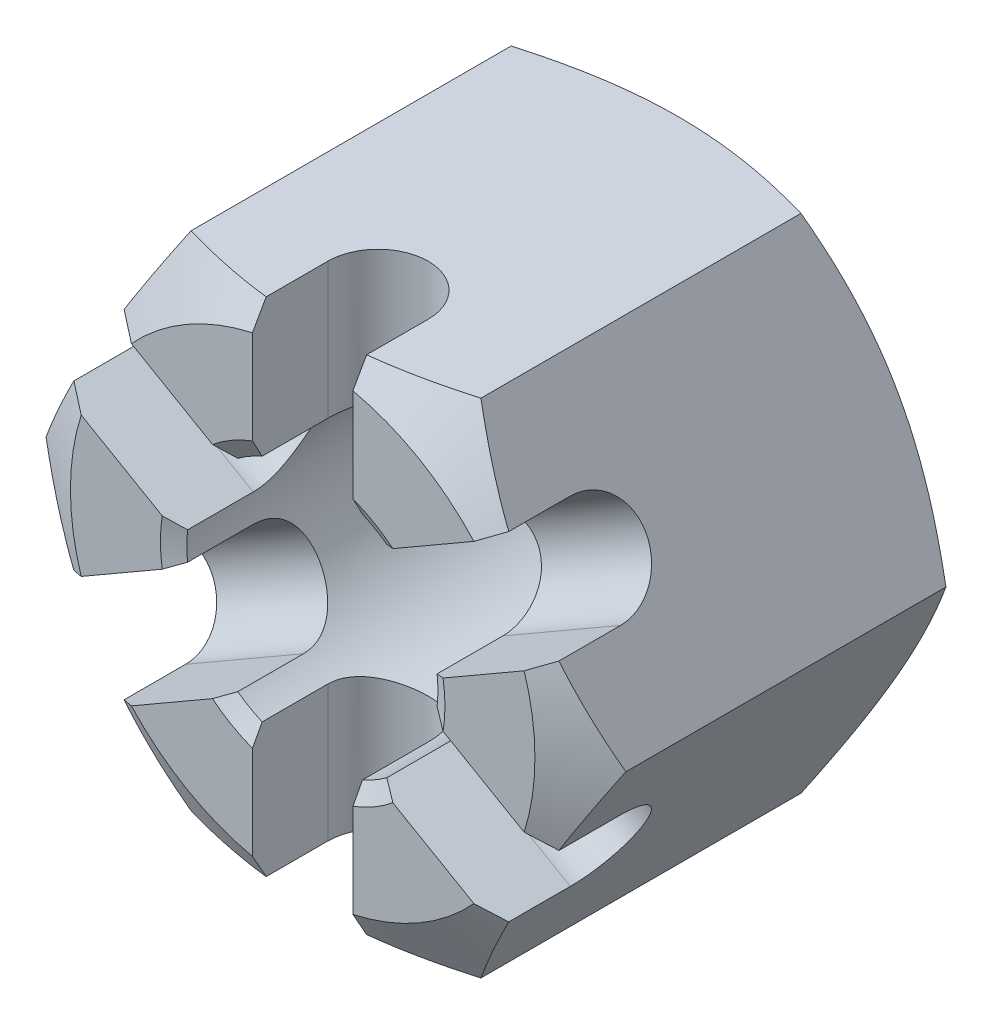
SolidWorks part; units mm, degrees
ref_plane "Front" through (0, 0, 0) normal (0, 0, 1) x (1, 0, 0)
ref_plane "Top" through (0, 0, 0) normal (0, 1, 0) x (1, 0, 0)
ref_plane "Right" through (0, 0, 0) normal (1, 0, 0) x (0, 0, -1)
sketch "Sketch1" plane through (0, 0, 0) normal (0, 0, 1) x (1, 0, 0)
  line L1 (2.8868, -5) -> (5.7735, 0)
  line L2 (5.7735, 0) -> (2.8868, 5)
  line L3 (2.8868, 5) -> (-2.8868, 5)
  line L4 (-2.8868, 5) -> (-5.7735, 0)
  line L5 (-5.7735, 0) -> (-2.8868, -5)
  line L6 (-2.8868, -5) -> (2.8868, -5)
  circle A0 centre (0, 0) radius 5 construction
  circle A1 centre (0, 0) radius 2.5
extrude "BaseNut" add sketch "Sketch1" against normal blind 7.7
cosmetic thread "ThreadCosmetic1" [suppressed] parameters "D"=6
sketch "Sketch2" plane through (0, 0, 0) normal (0, 1, 0) x (1, 0, 0)
  line L0 (-5.7735, 7.7) -> (-4.625, 7.7)
  line L2 (-4.625, 7.7) -> (-5.7735, 7.0369)
  line L3 (-5.7735, 7.0369) -> (-5.7735, 7.7)
  line L4 (0, 3.3759) -> (0, -9.8171) construction
  line L6 (-9.7712, 3.85) -> (9.8853, 3.85) construction
  line L7 (-5.7735, 0.6631) -> (-5.7735, 0)
  line L8 (-4.625, 0) -> (-5.7735, 0.6631)
  line L9 (-5.7735, 0) -> (-4.625, 0)
  dimension "D1" = 30
  dimension "D2" = 3.85
revolve "Double-Chamfer" cut sketch "Sketch2" angle 360 about L4
chamfer "EndChamfer" distance 0.3333 angle 30 2 edges at (2.5, 0, -7.7) (2.5, 0, 0) first distance on face at (2.5, 0, -7.7) first distance on face at (-4.625, 0, 0)
sketch "Sketch3" plane through (0, 0, 0) normal (0, 1, 0) x (1, 0, 0)
  line L0 (0, 4.2201) -> (0, -10.5237) construction
  line L1 (-2.8333, 0) -> (2.8333, 0) construction
  line L2 (-1, 0) -> (-1, 1.5)
  line L3 (1, 0) -> (1, 1.5)
  line L4 (2.6925, 7.7) -> (-2.6925, 7.7) construction
  arc A0 (-1, 1.5) -> (1, 1.5) centre (0, 1.5) cw
  point P2 (0, 2.5)
  point P3 (0, 7.7)
  dimension "D1" = 2.5
  dimension "W" = 5.2
extrude "Slot" cut sketch "Sketch3" against normal through all and the other way through all
ref_axis "Axis1" through (0, 0, 9.8171) along (0, 0, -1)
pattern_circular "SlotPattern" count 3 over 360 about axis through (0, 0, -3.3759) along (0, 0, 1) of "Slot"
sketch "Sketch4" plane through (0, 0, 0) normal (0, 1, 0) x (1, 0, 0)
  line L0 (0, 8.8442) -> (0, -1.346) construction
  line L1 (2, 7.6167) -> (2.5, 7.6167)
  line L2 (2.5, 7.6167) -> (2.933, 7.3667)
  line L3 (2.933, 7.3667) -> (2.5, 7.1167)
  line L4 (2.5, 7.1167) -> (2, 7.1167)
  line L5 (2, 7.1167) -> (2, 7.6167)
  line L6 (2.5, 7.3667) -> (-2.5, 7.3667) construction
  dimension "D1" = 0.5
  dimension "D2" = 5
revolve "Cut-Revolve10" [suppressed] cut sketch "Sketch4" angle 360 about L0
pattern_linear "LPattern10" [suppressed] count 12 spacing 0.6 along (0, 0, 1) of bodies 105
equation "\"dw@Sketch2\" = \"s@Sketch1\"-0.75"
equation "\"D1@Sketch3\" = \"m@BaseNut\" - \"W@Sketch3\""
equation "\"D2@Sketch2\" = \"m@BaseNut\" / 2"
equation "\"D1@Sketch4\" = (  \"D@ThreadCosmetic1\" - \"D@Sketch1\" )  / 2"
equation "\"D2@Sketch4\" = \"D@Sketch1\""
equation "\"D3@LPattern10\" = \"D1@Sketch4\" * 1.2"
equation "\"D1@LPattern10\" = \"m@BaseNut\" / \"D3@LPattern10\" - 1"
equation "\"D1@EndChamfer\" = \"D@Sketch1\" / 15"
